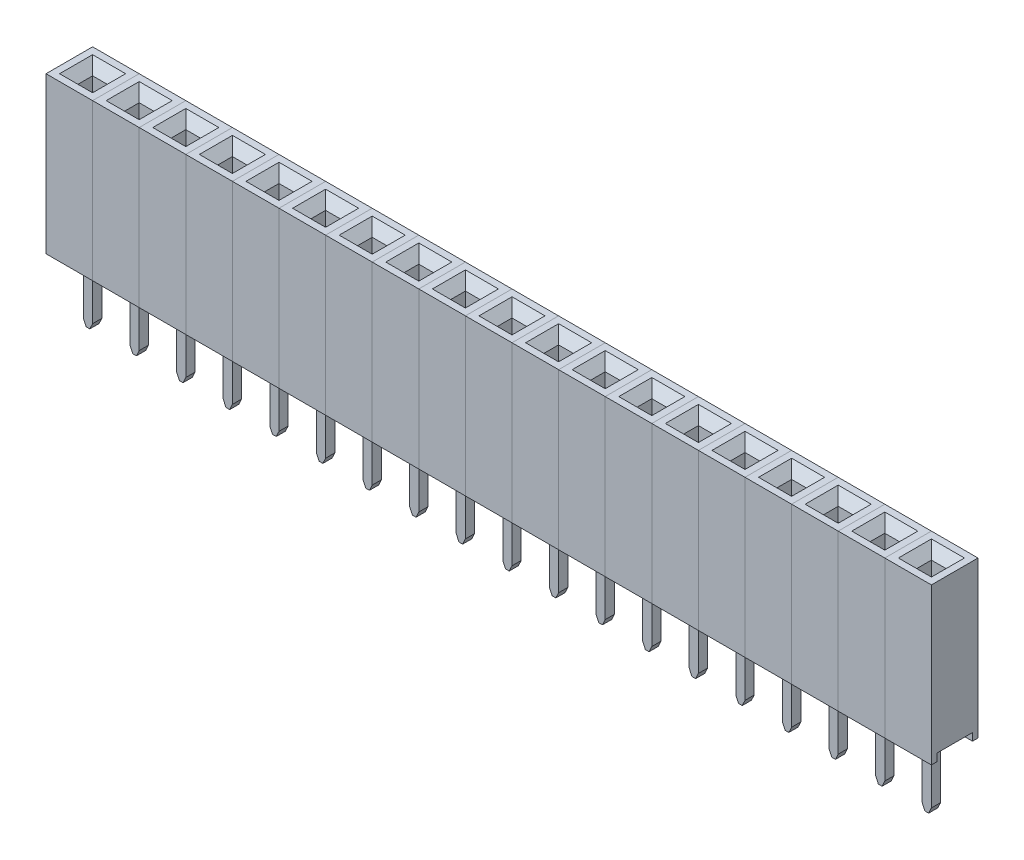
SolidWorks part; units mm, degrees
ref_plane "Front" through (0, 0, 0) normal (0, 0, 1) x (1, 0, 0)
ref_plane "Top" through (0, 0, 0) normal (0, 1, 0) x (1, 0, 0)
ref_plane "Right" through (0, 0, 0) normal (1, 0, 0) x (0, 0, -1)
sketch "Sketch1" plane through (0, 0, 0) normal (0, 0, 1) x (1, 0, 0)
  line L1 (1.27, -4.25) -> (-1.27, -4.25)
  line L2 (1.27, -4.25) -> (1.27, 4.25)
  line L3 (1.27, 4.25) -> (-1.27, 4.25)
  line L4 (-1.27, -4.25) -> (-1.27, 4.25)
  line L5 (1.27, -4.25) -> (-1.27, 4.25) construction
  line L6 (1.27, 4.25) -> (-1.27, -4.25) construction
  point P0 (0, 0)
  dimension "D1" = 2.54
  dimension "D2" = 8.5
extrude "Boss-Extrude1" add sketch "Sketch1" along normal mid plane 2.54
sketch "Sketch2" plane through (0, 0, 0) normal (1, 0, 0) x (0, 0, -1)
  line L0 (-0.97, -4.25) -> (0.97, -4.25)
  line L1 (-1.27, -4.25) -> (1.27, -4.25) construction
  line L2 (0.97, -4.25) -> (0.97, -3.8396)
  line L3 (0.97, -3.8396) -> (-0.97, -3.8396)
  line L4 (-0.97, -3.8396) -> (-0.97, -4.25)
  line L5 (1.27, -4.25) -> (1.27, 4.25) construction
  line L6 (-1.27, -4.25) -> (-1.27, 4.25) construction
  dimension "D1" = 0.3
  dimension "D2" = 0.3
extrude "Cut-Extrude1" cut sketch "Sketch2" against normal mid plane 100
sketch "Sketch4" plane through (0, 4.25, 0) normal (0, 1, 0) x (1, 0, 0)
  line L0 (-1.27, 0) -> (1.27, 0) construction
  line L1 (-1.27, -1.27) -> (-1.27, 1.27) construction
  line L2 (1.27, -1.27) -> (1.27, 1.27) construction
  line L4 (-0.875, 0.875) -> (0.875, 0.875)
  line L5 (-0.875, 0.875) -> (-0.875, -0.875)
  line L6 (-0.875, -0.875) -> (0.875, -0.875)
  line L7 (0.875, 0.875) -> (0.875, -0.875)
  line L8 (-0.875, 0.875) -> (0.875, -0.875) construction
  line L9 (-0.875, -0.875) -> (0.875, 0.875) construction
  line L10 (-0.4, 0.4) -> (0.4, 0.4)
  line L11 (-0.4, 0.4) -> (-0.4, -0.4)
  line L12 (-0.4, -0.4) -> (0.4, -0.4)
  line L13 (0.4, 0.4) -> (0.4, -0.4)
  line L14 (-0.4, 0.4) -> (0.4, -0.4) construction
  line L15 (-0.4, -0.4) -> (0.4, 0.4) construction
  point P6 (0, 0)
  point P11 (0, 0)
  point P16 (0, 0)
  dimension "D1" = 1.75
  dimension "D2" = 0.8
extrude "Cut-Extrude2" cut sketch "Sketch4" against normal blind 1.5 contours L13 L10 L11 L12 region at (0, 4.25, 0)
chamfer "Chamfer1" distance 0.5 angle 45 4 edges at (0, 4.25, -0.4) (-0.4, 4.25, 0) (0, 4.25, 0.4) (0.4, 4.25, 0)
sketch "Sketch5" plane through (0, 0, 0) normal (0, 1, 0) x (1, 0, 0)
  line L1 (-0.9, 0.9) -> (0.9, 0.9)
  line L2 (-0.9, 0.9) -> (-0.9, -0.9)
  line L3 (-0.9, -0.9) -> (0.9, -0.9)
  line L4 (0.9, 0.9) -> (0.9, -0.9)
extrude "Cut-Extrude3" cut sketch "Sketch5" against normal blind 3 and the other way blind 3
sketch "Sketch9" plane through (0, 0, 0) normal (0, 0, 1) x (1, 0, 0)
  line L0 (0, 1.6008) -> (0, -6.2684) construction
  line L1 (0.8528, -1.3416) -> (0.6022, -1.2609)
  line L2 (0.6022, -1.2609) -> (0.4133, 1.4919)
  line L3 (0.2803, 1.3393) -> (0.5075, -1.9717)
  line L4 (0.8528, -1.3416) -> (0.8528, -2.6933)
  line L5 (0.8528, -2.6933) -> (0.2807, -3.0533)
  line L6 (0.2807, -3.0533) -> (-0.2807, -3.0533)
  line L7 (-0.8528, -2.6933) -> (-0.2807, -3.0533)
  line L8 (-0.8528, -1.3416) -> (-0.8528, -2.6933)
  line L9 (-0.8528, -1.3416) -> (-0.6022, -1.2609)
  line L10 (-0.6022, -1.2609) -> (-0.4133, 1.4919)
  line L11 (-0.2803, 1.3393) -> (-0.5075, -1.9717)
  line L12 (-0.1, -7.6212) -> (0.1, -7.6212)
  line L13 (0.1, -7.6212) -> (0.25, -7.2995)
  line L14 (0.25, -7.2995) -> (0.25, -3.0533)
  line L15 (-0.1, -7.6212) -> (-0.25, -7.2995)
  line L16 (-0.25, -7.2995) -> (-0.25, -3.0533)
  line L19 (0, 0) -> (0, -10.2857) construction
  arc A0 (0.4133, 1.4919) -> (0.2803, 1.3393) centre (0.2705, 1.4821) ccw
  arc A1 (0.5075, -1.9717) -> (0, -2.3943) centre (0.101, -1.9996) cw
  arc A2 (-0.5075, -1.9717) -> (0, -2.3943) centre (-0.101, -1.9996) ccw
  arc A3 (-0.4133, 1.4919) -> (-0.2803, 1.3393) centre (-0.2705, 1.4821) cw
  point P16 (0, -3.0533)
  point P24 (-0.25, -4.3212)
  dimension "D1" = 115
  dimension "D2" = 115
  dimension "D3" = 0.25
  dimension "D4" = 0.2
  dimension "D5" = 0.25
  dimension "D6" = 3.3
extrude "Boss-Extrude4" add sketch "Sketch9" along normal mid plane 1.7 contours A1 L0 L6 L5 L4 L1 L2 A0 L3 | L0 A2 L11 A3 L10 L9 L8 L7 L6 region at (0.803, -2.0175, 0)
extrude "Boss-Extrude5" add sketch "Sketch9<3>" along normal mid plane 0.5 contours L16 L15 L12 L13 L14 L6 region at (0, -5.2903, 0)
sketch "Sketch9<3>" plane through (0, 0, 0) normal (0, 0, 1) x (1, 0, 0) same geometry as "Sketch9"
pattern_linear "LPattern1" count 19 spacing 2.54 along (1, 0, 0) of bodies 108
